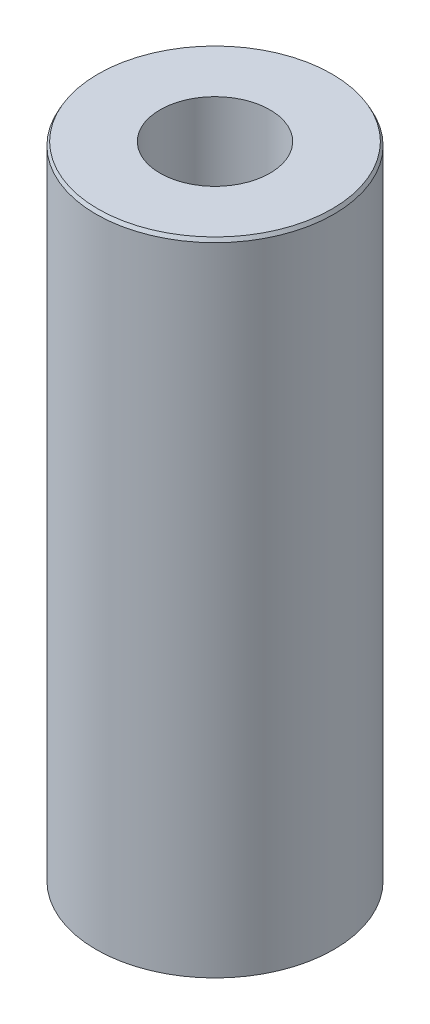
SolidWorks part; units mm, degrees
ref_plane "Front Plane" through (0, 0, 0) normal (0, 0, 1) x (1, 0, 0)
ref_plane "Top Plane" through (0, 0, 0) normal (0, 1, 0) x (1, 0, 0)
ref_plane "Right Plane" through (0, 0, 0) normal (1, 0, 0) x (0, 0, -1)
sketch "Sketch1" plane through (0, 0, 0) normal (0, 1, 0) x (1, 0, 0)
  circle A0 centre (0, 0) radius 27.5
  dimension "SHAFT_OD" = 55
extrude "Boss-Extrude1" add sketch "Sketch1" along normal blind 148.5892
sketch "Sketch2" plane through (0, 0, 0) normal (0, 1, 0) x (1, 0, 0)
  circle A0 centre (0, 0) radius 12.716
  dimension "BORE_D" = 25.432
extrude "Cut-Extrude1" cut sketch "Sketch2" along normal through all
chamfer "Chamfer1" distance 0.8315 angle 28.067 2 edges at (0, 148.5892, 27.5) (0, 0, 27.5) first distance on face at (0, 148.5892, 27.5) first distance on face at (0, 0, 12.716)
